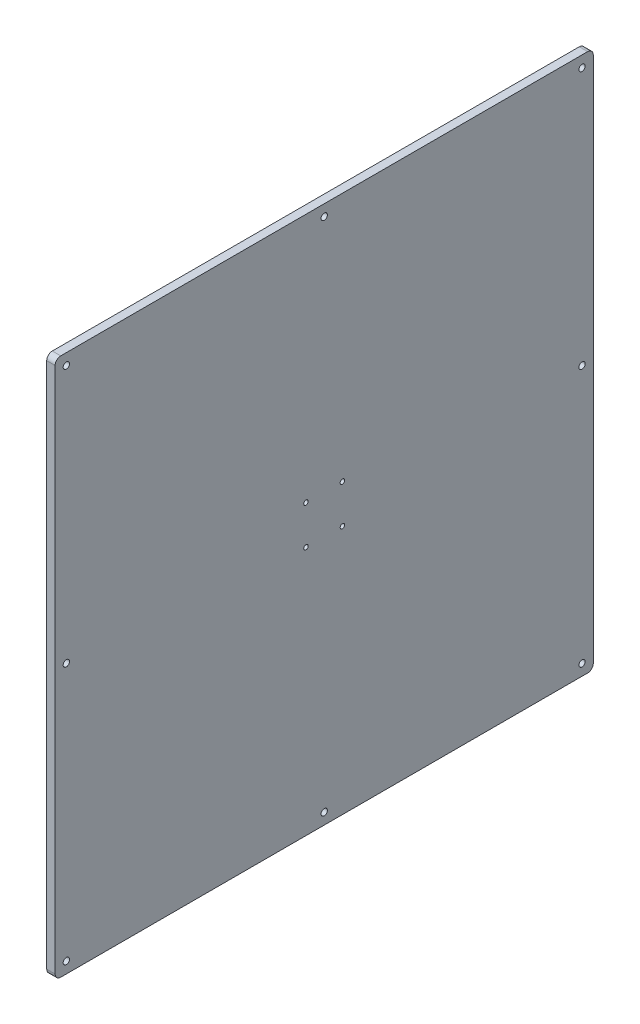
SolidWorks part; units mm, degrees
ref_plane "Front Plane" through (0, 0, 0) normal (0, 0, 1) x (1, 0, 0)
ref_plane "Top Plane" through (0, 0, 0) normal (0, 1, 0) x (1, 0, 0)
ref_plane "Right Plane" through (0, 0, 0) normal (1, 0, 0) x (0, 0, -1)
sketch "Sketch1" plane through (0, 0, 0) normal (1, 0, 0) x (0, 0, -1)
  line L1 (-304.8, -304.8) -> (304.8, -304.8)
  line L2 (-304.8, -304.8) -> (-304.8, 304.8)
  line L3 (-304.8, 304.8) -> (304.8, 304.8)
  line L4 (304.8, -304.8) -> (304.8, 304.8)
  line L5 (-304.8, -304.8) -> (304.8, 304.8) construction
  line L6 (-304.8, 304.8) -> (304.8, -304.8) construction
  point P0 (0, 0)
  point P5 (0, 0)
  dimension "D1" = 609.6
  dimension "D2" = 609.6
extrude "Boss-Extrude1" add sketch "Sketch1" along normal blind 9.525
hole_wizard "1/4-20 Tapped Hole1" positions "Sketch2" profile "Sketch3" tap size "1/4-20" standard "ANSI Inch" end condition through all
sketch "Sketch2" plane through (9.525, 0, 0) normal (1, 0, 0) x (0, 0, -1)
  line L1 (-20.6375, -21.9075) -> (20.6375, -21.9075) construction
  line L2 (-20.6375, -21.9075) -> (-20.6375, 21.9075) construction
  line L3 (-20.6375, 21.9075) -> (20.6375, 21.9075) construction
  line L4 (20.6375, -21.9075) -> (20.6375, 21.9075) construction
  line L5 (-20.6375, -21.9075) -> (20.6375, 21.9075) construction
  line L6 (-20.6375, 21.9075) -> (20.6375, -21.9075) construction
  point P0 (-20.6375, 21.9075)
  point P58 (20.6375, 21.9075)
  point P61 (20.6375, -21.9075)
  point P64 (-20.6375, -21.9075)
  dimension "D1" = 43.815
  dimension "D2" = 41.275
cosmetic thread "Hole Thread1" parameters "D2"=6.35
cosmetic thread "Hole Thread2" parameters "D2"=6.35
cosmetic thread "Hole Thread3" parameters "D2"=6.35
cosmetic thread "Hole Thread4" parameters "D2"=6.35
sketch "Sketch3" plane through (9.525, 21.9075, 20.6375) normal (0, 1, 0) x (0, 0, -1)
  line L0 (0, 0) -> (0, 9.525)
  line L1 (0, 9.525) -> (2.5527, 9.525)
  line L2 (2.5527, 9.525) -> (2.5527, 0)
  line L5 (2.5527, 0) -> (0, 0)
  line L11 (0, -6.35) -> (0, 107.95) construction
  dimension "Thru Tap Drill Dia." = 5.1054
  dimension "Thru Tap Drill Depth" = 9.525
sketch "Sketch4" plane through (9.525, 0, 0) normal (1, 0, 0) x (0, 0, -1)
  line L6 (304.8, 304.8) -> (-304.8, 304.8) construction
  line L7 (0, -304.8) -> (0, 304.8) construction
  line L14 (-304.8, -304.8) -> (304.8, -304.8) construction
  line L15 (-304.8, 0) -> (304.8, 0) construction
  line L22 (-304.8, 304.8) -> (-304.8, -304.8) construction
  line L23 (304.8, -304.8) -> (304.8, 304.8) construction
ref_axis "Axis1" through (0, 0, 0) along (1, 0, 0)
fillet "Fillet1" radius 6.35 4 edges at (4.7625, -304.8, 304.8) (4.7625, -304.8, -304.8) (4.7625, 304.8, -304.8) (4.7625, 304.8, 304.8)
hole_wizard "1/4 Clearance Hole1" positions "Sketch5" profile "Sketch6" hole size "1/4" standard "ANSI Inch" end condition through all
sketch "Sketch5" plane through (9.525, 0, 0) normal (1, 0, 0) x (0, 0, -1)
  line L0 (-304.8, 298.45) -> (-304.8, -298.45) construction
  line L1 (298.45, 304.8) -> (-298.45, 304.8) construction
  line L2 (-304.8, 0) -> (304.8, 0) construction
  line L4 (0, -304.8) -> (0, 304.8) construction
  line L5 (-292.1, 292.1) -> (292.1, 292.1) construction
  line L7 (-292.1, 292.1) -> (-292.1, -292.1) construction
  point P0 (-292.1, 292.1)
  point P17 (292.1, 292.1)
  point P18 (292.1, -292.1)
  point P19 (-292.1, -292.1)
  point P23 (0, 292.1)
  point P32 (-292.1, 0)
  point P35 (0, -292.1)
  point P36 (292.1, 0)
  dimension "D1" = 12.7
  dimension "D2" = 12.7
sketch "Sketch6" plane through (9.525, 292.1, 292.1) normal (0, 1, 0) x (0, 0, -1)
  line L0 (0, 0) -> (0, 9.525)
  line L1 (0, 9.525) -> (3.5712, 9.525)
  line L2 (3.5712, 9.525) -> (3.5712, 0)
  line L5 (3.5712, 0) -> (0, 0)
  line L11 (0, -6.35) -> (0, 107.95) construction
  dimension "Thru Hole Dia." = 7.1425
  dimension "Thru Hole Depth" = 9.525
